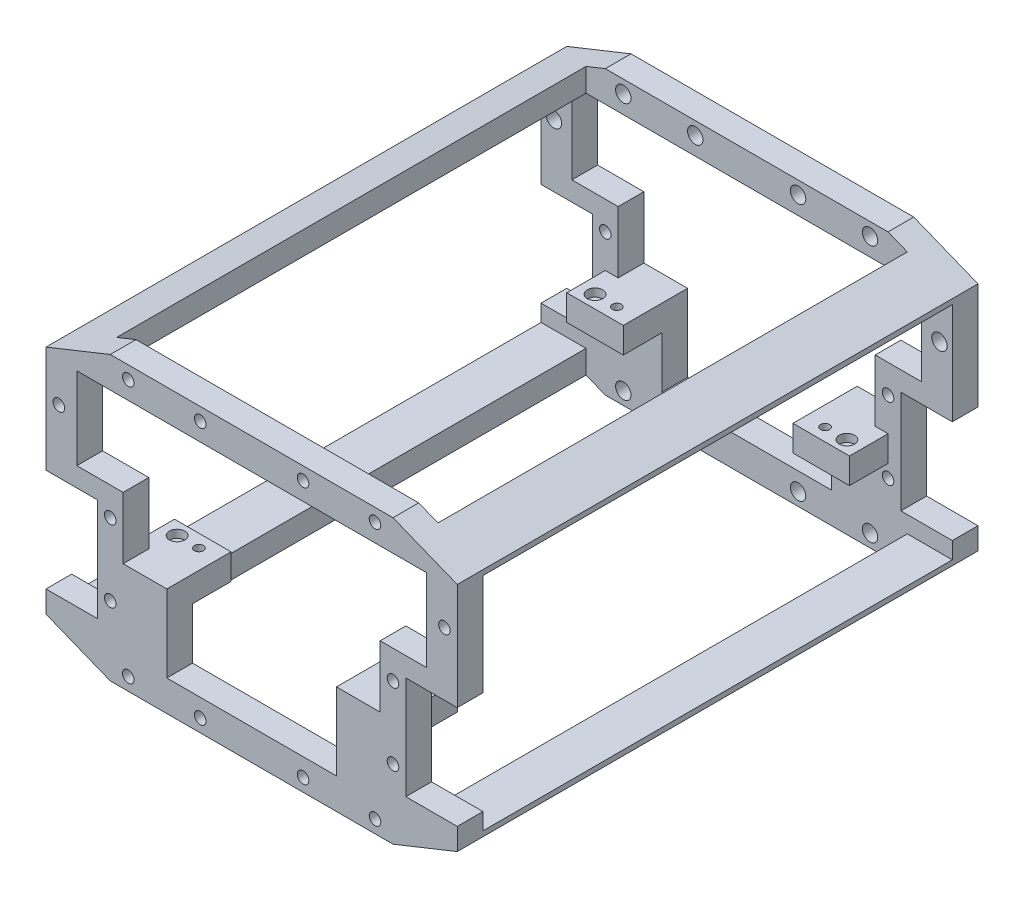
SolidWorks part; units mm, degrees
ref_plane "Ebene vorne" through (0, 0, 0) normal (0, 0, 1) x (1, 0, 0)
ref_plane "Ebene oben" through (0, 0, 0) normal (0, 1, 0) x (1, 0, 0)
ref_plane "Ebene rechts" through (0, 0, 0) normal (1, 0, 0) x (0, 0, -1)
sketch "Sketch1" plane through (0, 0, 0) normal (0, 0, 1) x (1, 0, 0)
  line L0 (6.3752, 91.162) -> (6.3752, 47.9643) construction
  line L5 (61.3752, -50.0357) -> (-48.6248, -50.0357)
  line L6 (86.3752, -40.0357) -> (86.3752, 49.9643)
  line L11 (61.3752, 59.9643) -> (-48.6248, 59.9643)
  line L12 (-73.6248, -40.0357) -> (-73.6248, 49.9643)
  line L17 (86.3752, -50.0357) -> (-73.6248, 59.9643) construction
  line L19 (86.3752, 59.9643) -> (-73.6248, -50.0357) construction
  line L20 (74.3752, -38.0357) -> (-61.6248, -38.0357)
  line L24 (74.3752, -38.0357) -> (74.3752, 47.9643)
  line L25 (74.3752, 47.9643) -> (-61.6248, 47.9643)
  line L30 (-61.6248, -38.0357) -> (-61.6248, 47.9643)
  line L43 (74.3752, -38.0357) -> (-61.6248, 47.9643) construction
  line L92 (74.3752, 47.9643) -> (-61.6248, -38.0357) construction
  line L117 (20.3752, 47.9643) -> (-7.6248, 47.9643)
  line L119 (13.3752, -38.0357) -> (-0.6248, -38.0357)
  line L121 (13.3752, 47.9643) -> (-0.6248, 47.9643)
  line L123 (13.3752, -38.0357) -> (6.3752, 4.9643) construction
  line L124 (6.3752, 4.9643) -> (-0.6248, -38.0357) construction
  line L130 (-48.6248, 59.9643) -> (-73.6248, 49.9643)
  line L131 (86.3752, 49.9643) -> (61.3752, 59.9643)
  line L132 (-48.6248, -50.0357) -> (-73.6248, -40.0357)
  line L133 (86.3752, -40.0357) -> (61.3752, -50.0357)
  line L134 (-73.6248, 4.9643) -> (85.3752, 4.9643) construction
  line L196 (-68.6248, 87.6925) -> (-68.6248, -54.0606) construction
  line L221 (6.3752, 4.9643) -> (6.3752, -91.162) construction
  circle A48 centre (-68.6248, 32.9643) radius 2.25
  circle A49 centre (-41.6248, 54.9643) radius 2.25
  circle A50 centre (-13.6248, 54.9643) radius 2.25
  circle A51 centre (26.3752, 54.9643) radius 2.25
  circle A52 centre (54.3752, 54.9643) radius 2.25
  circle A53 centre (81.3752, 32.9643) radius 2.25
  circle A54 centre (81.3752, 4.9643) radius 2.25
  circle A55 centre (81.3752, -23.0357) radius 2.25
  circle A56 centre (54.3752, -45.0357) radius 2.25
  circle A57 centre (26.3752, -45.0357) radius 2.25
  circle A58 centre (-13.6248, -45.0357) radius 2.25
  circle A59 centre (-41.6248, -45.0357) radius 2.25
  circle A60 centre (-68.6248, -23.0357) radius 2.25
  circle A61 centre (-68.6248, 4.9643) radius 2.25
  point P0 (6.3752, 4.9643)
  point P5 (6.3752, 4.9643)
  point P12 (6.3752, 4.9643)
  point P15 (6.3752, 47.9643)
  point P21 (-68.6248, 32.9643)
  point P22 (-41.6248, 54.9643)
  point P23 (-13.6248, 54.9643)
  point P24 (26.3752, 54.9643)
  point P26 (54.3752, 54.9643)
  point P27 (81.3752, 32.9643)
  point P28 (81.3752, 4.9643)
  point P29 (81.3752, -23.0357)
  point P33 (54.3752, -45.0357)
  point P34 (26.3752, -45.0357)
  point P35 (-13.6248, -45.0357)
  point P36 (-41.6248, -45.0357)
  point P62 (6.3752, 53.9643)
  point P162 (-68.6248, -23.0357)
  point P163 (-68.6248, 4.9643)
  dimension "D1" = 4.5
  dimension "D2" = 5
  dimension "D3" = 5
  dimension "D4" = 5
extrude "Boss-Extrude2" add sketch "Sketch1" along normal blind 202.6 contours L133 L6 L131 L11 L130 L12 L132 L5 A61 A60 A59 A58 A57 A56 A55 A54 A53 A52 A51 A50 A49 A48 L20 L30 L25 L117 L24 region at (6.3752, -48.0941, 0)
sketch "Sketch2" plane through (-73.6248, 0, 0) normal (-1, 0, 0) x (0, 0, 1)
  line L0 (0, 49.9643) -> (202.6, -40.0357) construction
  line L1 (202.6, -40.0357) -> (202.6, 49.9643) construction
  line L2 (10, -38.0357) -> (192.6, -38.0357)
  line L3 (10, -38.0357) -> (10, 47.9643)
  line L4 (10, 47.9643) -> (192.6, 47.9643)
  line L5 (192.6, -38.0357) -> (192.6, 47.9643)
  line L6 (10, -38.0357) -> (192.6, 47.9643) construction
  line L7 (10, 47.9643) -> (192.6, -38.0357) construction
  line L8 (202.6, 49.9643) -> (0, 49.9643) construction
  point P4 (101.3, 4.9643)
  dimension "D1" = 10
  dimension "D2" = 2
sketch "Sketch3" plane through (0, 59.9643, 0) normal (0, 1, 0) x (1, 0, 0)
  line L0 (-48.6248, 0) -> (61.3752, -202.6) construction
  line L1 (61.3752, 0) -> (-48.6248, 0) construction
  line L2 (61.3752, -192.6) -> (-48.6248, -192.6)
  line L3 (61.3752, -192.6) -> (61.3752, -10)
  line L4 (61.3752, -10) -> (-48.6248, -10)
  line L5 (-48.6248, -192.6) -> (-48.6248, -10)
  line L6 (61.3752, -192.6) -> (-48.6248, -10) construction
  line L7 (61.3752, -10) -> (-48.6248, -192.6) construction
  line L8 (61.3752, -202.6) -> (61.3752, 0) construction
  point P4 (6.3752, -101.3)
  dimension "D1" = 10
  dimension "D2" = 0
extrude "Cut-Extrude1" cut sketch "Sketch2" against normal through all
sketch "Sketch4" plane through (0, 0, 10) normal (0, 0, 1) x (1, 0, 0)
  circle A0 centre (-68.6248, 32.9643) radius 3
  circle A1 centre (-68.6248, 4.9643) radius 3
  circle A2 centre (-68.6248, -23.0357) radius 3
  circle A3 centre (-41.6248, 54.9643) radius 3
  circle A4 centre (-13.6248, 54.9643) radius 3
  circle A5 centre (26.3752, 54.9643) radius 3
  circle A6 centre (54.3752, 54.9643) radius 3
  circle A7 centre (81.3752, 32.9643) radius 3
  circle A8 centre (81.3752, 4.9643) radius 3
  circle A9 centre (81.3752, -23.0357) radius 3
  circle A10 centre (54.3752, -45.0357) radius 3
  circle A11 centre (26.3752, -45.0357) radius 3
  circle A12 centre (-13.6248, -45.0357) radius 3
  circle A13 centre (-41.6248, -45.0357) radius 3
  dimension "D1" = 6
extrude "Cut-Extrude2" cut sketch "Sketch4" against normal blind 4.5
extrude "Cut-Extrude3" cut sketch "Sketch4<2>" along normal blind 4.5 from surface starting at face at (-66.3748, 32.9643, 192.6)
sketch "Sketch4<2>" plane through (0, 0, 10) normal (0, 0, 1) x (1, 0, 0) same geometry as "Sketch4"
extrude "Cut-Extrude4" cut sketch "Sketch3" against normal through all
sketch "Sketch5" plane through (0, -38.0357, 0) normal (0, 1, 0) x (1, 0, 0)
  line L0 (-48.6248, -10) -> (61.3752, -192.6) construction
  line L1 (61.3752, -10) -> (-48.6248, -10) construction
  line L2 (-56.1248, -192.6) -> (68.8752, -192.6)
  line L3 (-56.1248, -192.6) -> (-56.1248, -10)
  line L4 (-56.1248, -10) -> (68.8752, -10)
  line L5 (68.8752, -192.6) -> (68.8752, -10)
  line L6 (-56.1248, -192.6) -> (68.8752, -10) construction
  line L7 (-56.1248, -10) -> (68.8752, -192.6) construction
  point P4 (6.3752, -101.3)
  dimension "D1" = 125
extrude "Cut-Extrude5" cut sketch "Sketch5" along normal through all from surface starting at face at (6.3752, -50.0357, 197.6)
sketch "Sketch6" plane through (86.3752, 0, 0) normal (1, 0, 0) x (0, 0, -1)
  line L0 (-202.6, -38.0357) -> (-202.6, -31.5357) construction
  line L1 (-202.6, -40.0357) -> (-202.6, 49.9643) construction
  line L2 (-101.3, 56.9643) -> (-101.3, -47.0357) construction
  line L3 (-202.6, -31.5357) -> (-182.6, -31.5357)
  line L4 (-202.6, -31.5357) -> (-202.6, 8.4643)
  line L5 (-202.6, 8.4643) -> (-182.6, 8.4643)
  line L6 (-182.6, -31.5357) -> (-182.6, 8.4643)
  line L7 (-10, 56.9643) -> (-192.6, 56.9643) construction
  line L8 (-10, -47.0357) -> (-192.6, -47.0357) construction
  line L9 (0, -31.5357) -> (-20, -31.5357)
  line L10 (-20, -31.5357) -> (-20, 8.4643)
  line L11 (0, -31.5357) -> (0, 8.4643)
  line L12 (0, 8.4643) -> (-20, 8.4643)
  dimension "D1" = 6.5
  dimension "D2" = 40
  dimension "D3" = 20
extrude "Cut-Extrude7" cut sketch "Sketch6" against normal up to next
sketch "Sketch8" plane through (0, 0, 202.6) normal (0, 0, 1) x (1, 0, 0)
  line L0 (86.3752, -31.5357) -> (66.3752, -31.5357) construction
  line L1 (86.3752, 8.4643) -> (66.3752, 8.4643) construction
  line L2 (66.3752, 8.4643) -> (66.3752, -31.5357)
  line L3 (66.3752, -31.5357) -> (74.3752, -31.5357)
  line L4 (74.3752, -31.5357) -> (74.3752, -38.0357)
  line L5 (74.3752, -38.0357) -> (56.3752, -38.0357)
  line L6 (74.3752, -38.0357) -> (-61.6248, -38.0357) construction
  line L7 (56.3752, -38.0357) -> (56.3752, 15.9987)
  line L8 (56.3752, 15.9987) -> (74.3752, 15.9987)
  line L9 (74.3752, 8.4643) -> (74.3752, 47.9643) construction
  line L10 (66.3752, 8.4643) -> (74.3752, 8.4643)
  line L11 (74.3752, 8.4643) -> (74.3752, 15.9987)
  line L12 (61.3752, -38.0357) -> (61.3752, 15.9987) construction
  line L13 (-68.6248, 4.9643) -> (61.3752, 4.9643) construction
  line L14 (-68.6248, -23.0357) -> (61.3752, -23.0357) construction
  circle A0 centre (61.3752, 4.9643) radius 2.25
  circle A1 centre (61.3752, -23.0357) radius 2.25
  dimension "D4" = 4.5
  dimension "D1" = 20
  dimension "D2" = 18
  dimension "D3" = 5
extrude "Boss-Extrude3" add sketch "Sketch8" against normal up to surface (10 mm away) up to face at (84.3752, 32.9643, 192.6)
ref_plane "Plane1" through (6.3752, 0, 0) normal (1, 0, 0) x (0, 0, -1)
extrude "Boss-Extrude4" add sketch "Sketch8<2>" against normal up to surface (202.6 mm away) from surface up to face at (-66.3748, 4.9643, 0) starting at face at (84.3752, 32.9643, 10)
sketch "Sketch8<2>" plane through (0, 0, 202.6) normal (0, 0, 1) x (1, 0, 0) same geometry as "Sketch8"
mirror "Mirror1" about plane through (6.3752, 0, 0) normal (1, 0, 0) of "Boss-Extrude4", "Boss-Extrude3", "Cut-Extrude7"
sketch "Sketch9" plane through (0, -38.0357, 0) normal (0, 1, 0) x (1, 0, 0)
  line L0 (-73.6248, -20) -> (86.3752, -20) construction
  line L1 (-73.6248, -10) -> (-73.6248, -192.6) construction
  line L2 (86.3752, -10) -> (86.3752, -192.6) construction
  line L3 (-43.6248, -10) -> (56.3752, -10) construction
  line L4 (-56.1248, -192.6) -> (-56.1248, -10) construction
  line L5 (-26.6248, -25) -> (-41.6248, -25)
  line L6 (-26.6248, -25) -> (-26.6248, -15)
  line L7 (-26.6248, -15) -> (-41.6248, -15) construction
  line L8 (-41.6248, -25) -> (-41.6248, -15)
  line L9 (-26.6248, -25) -> (-41.6248, -15) construction
  line L10 (-26.6248, -15) -> (-41.6248, -25) construction
  line L11 (-41.6248, -15) -> (-26.6248, -15)
  line L12 (-41.6248, -15) -> (-41.6248, 0)
  line L13 (-41.6248, 0) -> (-26.6248, 0)
  line L14 (-26.6248, -15) -> (-26.6248, 0)
  line L16 (-48.6248, 0) -> (-41.6248, 0)
  line L17 (-48.6248, 0) -> (-48.6248, -25)
  line L18 (-48.6248, -25) -> (-41.6248, -25)
  line L19 (-41.6248, 0) -> (-41.6248, -25)
  circle A0 centre (-34.1248, -20) radius 1.75
  point P8 (-34.1248, -20)
  line M6 (56.3752, 0) -> (-43.6248, 0)
  line M7 (-43.6248, 0) -> (-43.6248, -10)
  line M8 (-43.6248, -10) -> (56.3752, -10)
  dimension "D5" = 3.5
  dimension "D1" = 10
  dimension "D2" = 22
  dimension "D3" = 15
  dimension "D4" = 10
  dimension "D6" = 10
extrude "Boss-Extrude5" add sketch "Sketch9" against normal blind 10 from offset 30 contours L17 L18 L8 L12 L16 M8 M7 | L12 M8 M6 M7 | L14 L12 M8 M6 | L11 L14 L12 M8 | L11 L8 L5 L6 A0 region at (-34.1248, -38.0357, 24.8197) region at (-45.4474, -38.0357, 13.4677) region at (-34.1248, -38.0357, 12.5) region at (-34.1248, -38.0357, 5) region at (-42.6248, -38.0357, 5)
sketch "Sketch10" plane through (0, -18.0357, 0) normal (0, -1, 0) x (1, 0, 0)
  line L1 (-26.6248, 0) -> (-48.6248, 0)
  line L2 (-26.6248, 0) -> (-26.6248, 10)
  line L3 (-26.6248, 10) -> (-48.6248, 10)
  line L4 (-48.6248, 0) -> (-48.6248, 10)
extrude "Boss-Extrude6" add sketch "Sketch10" along normal blind 20
ref_plane "Plane2" through (0, 0, 101.3) normal (0, 0, 1) x (1, 0, 0)
mirror "Mirror2" about plane through (0, 0, 101.3) normal (0, 0, 1) of "Boss-Extrude6", "Boss-Extrude5"
mirror "Mirror3" about plane through (6.3752, 0, 0) normal (1, 0, 0) of "Boss-Extrude5", "Boss-Extrude6", "Mirror2"
sketch "Sketch11" plane through (0, 0, 202.6) normal (0, 0, 1) x (1, 0, 0)
  line L0 (-48.6248, -25.2857) -> (-48.6248, -20.7857) construction
  line L1 (61.3752, -25.2857) -> (61.3752, -20.7857) construction
  circle A0 centre (-48.6248, -23.0357) radius 2.25
  circle A1 centre (61.3752, -23.0357) radius 2.25
extrude "Cut-Extrude8" cut sketch "Sketch11" against normal through all
sketch "Sketch12" plane through (0, -8.0357, 0) normal (0, 1, 0) x (1, 0, 0)
  line L0 (-48.6248, -20) -> (61.3752, -20) construction
  line L1 (-48.6248, -10) -> (-48.6248, -25) construction
  line L2 (61.3752, -10) -> (61.3752, -25) construction
  line L3 (61.3752, -10) -> (-48.6248, -10) construction
  line L4 (-73.6248, -101.3) -> (86.3752, -101.3) construction
  line L5 (-73.6248, -202.6) -> (-73.6248, 0) construction
  line L6 (86.3752, -202.6) -> (86.3752, 0) construction
  circle A2 centre (-42.6248, -20) radius 3
  circle A3 centre (55.3752, -20) radius 3
  circle A4 centre (46.8752, -20) radius 1.75 construction
  circle A5 centre (-34.1248, -20) radius 1.75 construction
  circle A6 centre (55.3752, -182.6) radius 3
  circle A7 centre (-42.6248, -182.6) radius 3
  dimension "D2" = 6
  dimension "D3" = 6
  dimension "D5" = 8.5
  dimension "D4" = 8.5
  dimension "D1" = 10
extrude "Cut-Extrude9" cut sketch "Sketch12" against normal blind 3.1
